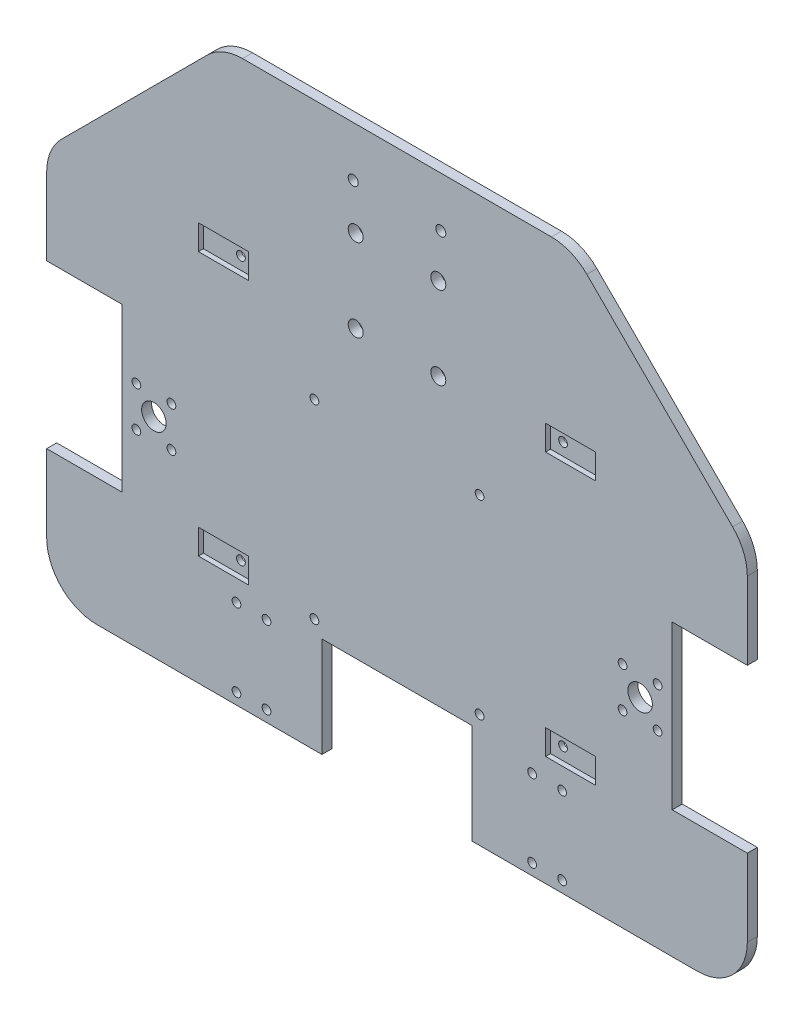
SolidWorks part; units mm, degrees
ref_plane "前视基准面" through (0, 0, 0) normal (0, 0, 1) x (1, 0, 0)
ref_plane "上视基准面" through (0, 0, 0) normal (0, 1, 0) x (1, 0, 0)
ref_plane "右视基准面" through (0, 0, 0) normal (1, 0, 0) x (0, 0, -1)
sketch "草图3" plane through (0, 0, 0) normal (0, 0, 1) x (1, 0, 0)
  line L1 (73.5057, 259.0895) -> (196.9372, 259.0895)
  line L2 (-4.7785, 180.8052) -> (-4.7785, 54.0895)
  line L3 (15.2215, 34.0895) -> (255.2215, 34.0895)
  line L4 (275.2215, 180.8052) -> (275.2215, 54.0895)
  line L6 (1.0793, 194.9474) -> (59.3636, 253.2316)
  line L9 (211.0793, 253.2316) -> (269.3636, 194.9474)
  arc A0 (73.5057, 259.0895) -> (59.3636, 253.2316) centre (73.5057, 239.0895) ccw
  arc A1 (211.0793, 253.2316) -> (196.9372, 259.0895) centre (196.9372, 239.0895) ccw
  arc A2 (1.0793, 194.9474) -> (-4.7785, 180.8052) centre (15.2215, 180.8052) ccw
  arc A3 (-4.7785, 54.0895) -> (15.2215, 34.0895) centre (15.2215, 54.0895) ccw
  arc A4 (255.2215, 34.0895) -> (275.2215, 54.0895) centre (255.2215, 54.0895) ccw
  arc A5 (275.2215, 180.8052) -> (269.3636, 194.9474) centre (255.2215, 180.8052) ccw
  dimension "D1" = 20
  dimension "D2" = 20
  dimension "D3" = 20
extrude "凸台-拉伸1" add sketch "草图3" along normal blind 4
sketch "电池槽" plane through (0, 0, 0) normal (0, 0, 1) x (1, 0, 0)
  line L0 (135.2215, 259.0895) -> (135.2215, 34.0895) construction
  line L6 (59.3636, 253.2316) -> (1.0793, 194.9474)
  line L7 (-4.7785, 180.8052) -> (-4.7785, 54.0895)
  line L8 (15.2215, 34.0895) -> (255.2215, 34.0895)
  line L9 (275.2215, 54.0895) -> (275.2215, 180.8052)
  line L10 (269.3636, 194.9474) -> (211.0793, 253.2316)
  line L11 (196.9372, 259.0895) -> (73.5057, 259.0895)
  line L12 (59.3636, 253.2316) -> (1.0793, 194.9474)
  line L13 (-4.7785, 180.8052) -> (-4.7785, 54.0895)
  line L14 (15.2215, 34.0895) -> (255.2215, 34.0895)
  line L15 (275.2215, 54.0895) -> (275.2215, 180.8052)
  line L16 (269.3636, 194.9474) -> (211.0793, 253.2316)
  line L17 (196.9372, 259.0895) -> (73.5057, 259.0895)
  line L21 (-4.7785, 117.4474) -> (275.2215, 117.4474) construction
  line L22 (95.2215, 162.4474) -> (175.2215, 162.4474)
  line L24 (105.2215, 152.4474) -> (165.2215, 152.4474)
  line L25 (105.2215, 152.4474) -> (105.2215, 82.4474)
  line L26 (105.2215, 82.4474) -> (165.2215, 82.4474)
  line L27 (165.2215, 152.4474) -> (165.2215, 82.4474)
  line L28 (105.2215, 152.4474) -> (165.2215, 82.4474) construction
  line L29 (105.2215, 82.4474) -> (165.2215, 152.4474) construction
  line L30 (175.2215, 162.4474) -> (175.2215, 72.4474)
  line L31 (95.2215, 72.4474) -> (175.2215, 72.4474)
  line L32 (95.2215, 162.4474) -> (95.2215, 72.4474)
  line L33 (95.2215, 162.4474) -> (105.2215, 152.4474) construction
  line L34 (105.2215, 82.4474) -> (95.2215, 72.4474) construction
  line L35 (165.2215, 82.4474) -> (175.2215, 72.4474) construction
  line L36 (165.2215, 152.4474) -> (175.2215, 162.4474) construction
  line L37 (97.2215, 160.4474) -> (173.2215, 160.4474)
  line L38 (173.2215, 160.4474) -> (173.2215, 74.4474)
  line L39 (97.2215, 74.4474) -> (173.2215, 74.4474)
  line L40 (97.2215, 160.4474) -> (97.2215, 74.4474)
  arc A6 (73.5057, 259.0895) -> (59.3636, 253.2316) centre (73.5057, 239.0895) ccw
  arc A7 (1.0793, 194.9474) -> (-4.7785, 180.8052) centre (15.2215, 180.8052) ccw
  arc A8 (-4.7785, 54.0895) -> (15.2215, 34.0895) centre (15.2215, 54.0895) ccw
  arc A9 (255.2215, 34.0895) -> (275.2215, 54.0895) centre (255.2215, 54.0895) ccw
  arc A10 (275.2215, 180.8052) -> (269.3636, 194.9474) centre (255.2215, 180.8052) ccw
  arc A11 (211.0793, 253.2316) -> (196.9372, 259.0895) centre (196.9372, 239.0895) ccw
  arc A12 (73.5057, 259.0895) -> (59.3636, 253.2316) centre (73.5057, 239.0895) ccw
  arc A13 (1.0793, 194.9474) -> (-4.7785, 180.8052) centre (15.2215, 180.8052) ccw
  arc A14 (-4.7785, 54.0895) -> (15.2215, 34.0895) centre (15.2215, 54.0895) ccw
  arc A15 (255.2215, 34.0895) -> (275.2215, 54.0895) centre (255.2215, 54.0895) ccw
  arc A16 (275.2215, 180.8052) -> (269.3636, 194.9474) centre (255.2215, 180.8052) ccw
  arc A17 (211.0793, 253.2316) -> (196.9372, 259.0895) centre (196.9372, 239.0895) ccw
  circle A20 centre (168.2215, 155.4474) radius 1.75
  circle A21 centre (168.2215, 79.4474) radius 1.75
  circle A22 centre (102.2215, 79.4474) radius 1.75
  circle A23 centre (102.2215, 155.4474) radius 1.75
  point P18 (135.2215, 117.4474)
  dimension "D3" = 8
  dimension "D2" = 10
  dimension "D1" = 0
sketch "轮槽" plane through (0, 0, 4) normal (0, 0, 1) x (1, 0, 0)
  line L4 (245.2215, 84.9474) -> (275.2215, 84.9474)
  line L5 (-4.7785, 149.9474) -> (7.2215, 149.9474)
  line L6 (59.3636, 253.2316) -> (1.0793, 194.9474)
  line L7 (-4.7785, 180.8052) -> (-4.7785, 54.0895)
  line L8 (15.2215, 34.0895) -> (255.2215, 34.0895)
  line L9 (275.2215, 54.0895) -> (275.2215, 180.8052)
  line L10 (269.3636, 194.9474) -> (211.0793, 253.2316)
  line L11 (196.9372, 259.0895) -> (73.5057, 259.0895)
  line L12 (59.3636, 253.2316) -> (1.0793, 194.9474)
  line L13 (-4.7785, 180.8052) -> (-4.7785, 54.0895)
  line L14 (15.2215, 34.0895) -> (255.2215, 34.0895)
  line L15 (275.2215, 54.0895) -> (275.2215, 180.8052)
  line L16 (269.3636, 194.9474) -> (211.0793, 253.2316)
  line L17 (196.9372, 259.0895) -> (73.5057, 259.0895)
  line L18 (7.2215, 149.9474) -> (25.2215, 149.9474)
  line L19 (25.2215, 149.9474) -> (25.2215, 84.9474)
  line L20 (25.2215, 84.9474) -> (-4.7785, 84.9474)
  line L21 (245.2215, 149.9474) -> (245.2215, 84.9474)
  line L22 (275.2215, 149.9474) -> (263.2215, 149.9474)
  line L23 (263.2215, 149.9474) -> (245.2215, 149.9474)
  arc A6 (73.5057, 259.0895) -> (59.3636, 253.2316) centre (73.5057, 239.0895) ccw
  arc A7 (1.0793, 194.9474) -> (-4.7785, 180.8052) centre (15.2215, 180.8052) ccw
  arc A8 (-4.7785, 54.0895) -> (15.2215, 34.0895) centre (15.2215, 54.0895) ccw
  arc A9 (255.2215, 34.0895) -> (275.2215, 54.0895) centre (255.2215, 54.0895) ccw
  arc A10 (275.2215, 180.8052) -> (269.3636, 194.9474) centre (255.2215, 180.8052) ccw
  arc A11 (211.0793, 253.2316) -> (196.9372, 259.0895) centre (196.9372, 239.0895) ccw
  arc A12 (73.5057, 259.0895) -> (59.3636, 253.2316) centre (73.5057, 239.0895) ccw
  arc A13 (1.0793, 194.9474) -> (-4.7785, 180.8052) centre (15.2215, 180.8052) ccw
  arc A14 (-4.7785, 54.0895) -> (15.2215, 34.0895) centre (15.2215, 54.0895) ccw
  arc A15 (255.2215, 34.0895) -> (275.2215, 54.0895) centre (255.2215, 54.0895) ccw
  arc A16 (275.2215, 180.8052) -> (269.3636, 194.9474) centre (255.2215, 180.8052) ccw
  arc A17 (211.0793, 253.2316) -> (196.9372, 259.0895) centre (196.9372, 239.0895) ccw
  line M18 (-4.7785, 180.8052) -> (-4.7785, 54.0895)
  line M22 (275.2215, 54.0895) -> (275.2215, 180.8052)
  dimension "D1" = 0
sketch "电机" plane through (0, 0, 0) normal (0, 0, 1) x (1, 0, 0)
  line L1 (31.0715, 125.4474) -> (45.0715, 125.4474) construction
  line L7 (25.2215, 130.6974) -> (53.2215, 130.6974) construction
  line L8 (245.2215, 122.9274) -> (237.0715, 122.9274) construction
  line L9 (45.0715, 125.4474) -> (31.0715, 125.4474) construction
  line L26 (53.2215, 130.6974) -> (53.2215, 104.1974) construction
  line L27 (25.2215, 117.4474) -> (33.3715, 117.4474) construction
  line L28 (217.2215, 122.9274) -> (225.3715, 122.9274) construction
  line L29 (225.3715, 122.9274) -> (225.3715, 130.9274) construction
  line L30 (25.2215, 111.9674) -> (25.2215, 104.1974) construction
  line L31 (239.3715, 130.9274) -> (225.3715, 130.9274) construction
  line L32 (232.3715, 130.9274) -> (232.3715, 114.9274) construction
  line L33 (237.0715, 122.9274) -> (225.3715, 122.9274) construction
  line L34 (225.3715, 114.9274) -> (239.3715, 114.9274) construction
  line L35 (135.2215, 259.0895) -> (135.2215, 34.0895) construction
  line L36 (196.9372, 259.0895) -> (73.5057, 259.0895) construction
  line L37 (15.2215, 34.0895) -> (255.2215, 34.0895) construction
  line L39 (45.0715, 117.4474) -> (45.0715, 125.4474) construction
  line L40 (45.0715, 109.4474) -> (31.0715, 109.4474) construction
  line L41 (38.0715, 125.4474) -> (38.0715, 109.4474) construction
  line L44 (25.2215, 111.9674) -> (25.2215, 130.6974) construction
  line L45 (53.2215, 104.1974) -> (25.2215, 104.1974) construction
  line L51 (53.2215, 117.4474) -> (45.0715, 117.4474) construction
  line L53 (245.2215, 117.4474) -> (245.2215, 109.6774) construction
  line L63 (237.0715, 117.4474) -> (225.3715, 117.4474) construction
  line L64 (245.2215, 111.9674) -> (245.2215, 130.6974) construction
  line L65 (217.2215, 130.6974) -> (217.2215, 104.1974)
  line L66 (245.2215, 104.1974) -> (245.2215, 130.6974)
  line L67 (217.2215, 117.4474) -> (225.3715, 117.4474) construction
  line L68 (217.2215, 104.1974) -> (245.2215, 104.1974) construction
  line L69 (245.2215, 111.9674) -> (245.2215, 130.6974) construction
  line L70 (232.3715, 125.4474) -> (232.3715, 109.4474) construction
  line L71 (225.3715, 109.4474) -> (239.3715, 109.4474) construction
  line L72 (225.3715, 117.4474) -> (225.3715, 125.4474) construction
  line L73 (245.2215, 111.9674) -> (245.2215, 104.1974) construction
  line L74 (245.2215, 130.6974) -> (217.2215, 130.6974)
  line L75 (217.2215, 104.1974) -> (245.2215, 104.1974)
  line L76 (245.2215, 117.4474) -> (237.0715, 117.4474) construction
  line L77 (217.2215, 130.6974) -> (217.2215, 104.1974) construction
  line L78 (225.3715, 125.4474) -> (239.3715, 125.4474) construction
  line L79 (245.2215, 130.6974) -> (217.2215, 130.6974) construction
  line L80 (239.3715, 125.4474) -> (225.3715, 125.4474) construction
  line L81 (25.2215, 111.9674) -> (25.2215, 130.6974) construction
  line L82 (33.3715, 117.4474) -> (45.0715, 117.4474) construction
  line L83 (25.2215, 117.4474) -> (25.2215, 109.6774) construction
  line L84 (45.0715, 114.9274) -> (31.0715, 114.9274) construction
  line L85 (33.3715, 122.9274) -> (45.0715, 122.9274) construction
  line L86 (38.0715, 130.9274) -> (38.0715, 114.9274) construction
  line L87 (31.0715, 130.9274) -> (45.0715, 130.9274) construction
  line L88 (45.0715, 122.9274) -> (45.0715, 130.9274) construction
  line L89 (53.2215, 122.9274) -> (45.0715, 122.9274) construction
  line L90 (25.2215, 122.9274) -> (33.3715, 122.9274) construction
  line L91 (53.2215, 104.1974) -> (25.2215, 104.1974)
  line L92 (25.2215, 130.6974) -> (53.2215, 130.6974)
  line L93 (25.2215, 104.1974) -> (25.2215, 130.6974)
  line L94 (53.2215, 130.6974) -> (53.2215, 104.1974)
  circle A27 centre (225.3715, 109.4474) radius 1.75
  circle A28 centre (239.3715, 125.4474) radius 1.75
  circle A29 centre (232.3715, 117.4474) radius 4.9
  circle A30 centre (225.3715, 125.4474) radius 1.75
  circle A31 centre (239.3715, 109.4474) radius 1.75
  circle A32 centre (31.0715, 109.4474) radius 1.75
  circle A33 centre (45.0715, 125.4474) radius 1.75
  circle A34 centre (38.0715, 117.4474) radius 4.9
  circle A35 centre (31.0715, 125.4474) radius 1.75
  circle A36 centre (45.0715, 109.4474) radius 1.75
sketch "L298N" plane through (0, 0, 0) normal (0, 0, 1) x (1, 0, 0)
  line L4 (113.7215, 226.2684) -> (156.7215, 226.2684)
  line L5 (113.7215, 226.2684) -> (113.7215, 183.2684)
  line L6 (113.7215, 183.2684) -> (156.7215, 183.2684)
  line L7 (156.7215, 226.2684) -> (156.7215, 183.2684)
  line L8 (113.7215, 226.2684) -> (156.7215, 183.2684) construction
  line L9 (113.7215, 183.2684) -> (156.7215, 226.2684) construction
  circle A0 centre (118.7215, 188.2684) radius 3
  circle A2 centre (118.7215, 221.2684) radius 3
  circle A3 centre (151.7215, 221.2684) radius 3
  circle A4 centre (151.7215, 188.2684) radius 3
  point P6 (135.2215, 204.7684)
  point P28 (135.2215, 204.7684)
  dimension "D1" = 4
extrude "切除-拉伸5" cut sketch "L298N" along normal blind 10 contours A0 | A2 | A4 | A3
extrude "切除-拉伸7" cut sketch "电池槽" along normal blind 10 contours A22 | A23 | A20 | A21
extrude "切除-拉伸8" cut sketch "轮槽" against normal blind 10 contours L20 L19 L18 L5 M18 | L22 L23 L21 L4 M22 region at (260.2215, 117.4474, 4) region at (10.2215, 117.4474, 4)
sketch "万向轮" plane through (0, 0, 0) normal (0, 0, 1) x (1, 0, 0)
  line L0 (135.2215, 259.0895) -> (135.2215, 219.0895) construction
  line L1 (196.9372, 259.0895) -> (73.5057, 259.0895) construction
  line L2 (158.7215, 239.0895) -> (111.7215, 239.0895) construction
  line L3 (152.7215, 239.0895) -> (117.7215, 239.0895)
  line L4 (111.7215, 239.0895) -> (125.647, 250.6363)
  line L5 (158.7215, 239.0895) -> (144.796, 250.6363)
  line L6 (158.7215, 239.0895) -> (144.796, 227.5426)
  line L7 (111.7215, 239.0895) -> (125.647, 227.5426)
  circle A0 centre (117.7215, 239.0895) radius 2
  circle A1 centre (152.7215, 239.0895) radius 2
  circle A2 centre (135.2215, 239.0895) radius 13.5
  circle A3 centre (135.2215, 239.0895) radius 15
  point P7 (135.2215, 239.0895)
  point P10 (135.2215, 239.0895)
extrude "切除-拉伸10" cut sketch "万向轮" along normal blind 10 contours A0 | A1 region at (152.7215, 241.0329, 0) region at (115.778, 239.0895, 0)
extrude "切除-拉伸3" cut sketch "电机" along normal blind 10 contours A32 | A33 | A34 | A35 | A36 | A30 | A28 | A31 | A27 | A29
ref_plane "基准面1" through (0, 0, 4) normal (0, 0, 1) x (1, 0, 0)
sketch "草图11" plane through (0, 0, 4) normal (0, 0, 1) x (1, 0, 0)
  line L0 (-3.2561, 188.4589) -> (273.6991, 188.4589) construction
  line L1 (65.8521, 132.7742) -> (204.5909, 132.7742) construction
  line L2 (15.2215, 34.0895) -> (255.2215, 34.0895) construction
  line L3 (204.5909, 257.5671) -> (204.5909, 34.0895) construction
  line L4 (-4.7785, 54.0895) -> (275.2215, 54.0895) construction
  line L6 (55.8521, 193.4589) -> (75.8521, 193.4589)
  line L7 (55.8521, 193.4589) -> (55.8521, 183.4589)
  line L8 (55.8521, 183.4589) -> (75.8521, 183.4589)
  line L9 (75.8521, 193.4589) -> (75.8521, 183.4589)
  line L10 (55.8521, 193.4589) -> (75.8521, 183.4589) construction
  line L11 (55.8521, 183.4589) -> (75.8521, 193.4589) construction
  line L14 (55.8521, 88.0895) -> (75.8521, 78.0895) construction
  line L15 (55.8521, 78.0895) -> (75.8521, 88.0895) construction
  line L16 (75.8521, 78.0895) -> (75.8521, 88.0895)
  line L17 (55.8521, 88.0895) -> (75.8521, 88.0895)
  line L18 (55.8521, 78.0895) -> (55.8521, 88.0895)
  line L19 (55.8521, 78.0895) -> (75.8521, 78.0895)
  line L20 (214.5909, 78.0895) -> (194.5909, 88.0895) construction
  line L21 (214.5909, 88.0895) -> (194.5909, 78.0895) construction
  line L22 (214.5909, 183.4589) -> (194.5909, 193.4589) construction
  line L23 (214.5909, 193.4589) -> (194.5909, 183.4589) construction
  line L24 (214.5909, 78.0895) -> (194.5909, 78.0895)
  line L25 (214.5909, 78.0895) -> (214.5909, 88.0895)
  line L26 (214.5909, 88.0895) -> (194.5909, 88.0895)
  line L27 (194.5909, 78.0895) -> (194.5909, 88.0895)
  line L28 (194.5909, 193.4589) -> (194.5909, 183.4589)
  line L29 (214.5909, 183.4589) -> (194.5909, 183.4589)
  line L30 (214.5909, 193.4589) -> (214.5909, 183.4589)
  line L31 (214.5909, 193.4589) -> (194.5909, 193.4589)
  arc A0 (1.0793, 194.9474) -> (-4.7785, 180.8052) centre (15.2215, 180.8052) ccw construction
  arc A1 (275.2215, 180.8052) -> (269.3636, 194.9474) centre (255.2215, 180.8052) ccw construction
  circle A2 centre (70.8521, 83.0895) radius 1.75
  arc A3 (211.0793, 253.2316) -> (196.9372, 259.0895) centre (196.9372, 239.0895) ccw construction
  arc A4 (-4.7785, 54.0895) -> (15.2215, 34.0895) centre (15.2215, 54.0895) ccw construction
  circle A9 centre (70.8521, 188.4589) radius 1.75
  circle A10 centre (199.5909, 83.0895) radius 1.75
  circle A11 centre (199.5909, 188.4589) radius 1.75
  point P26 (0, 0)
extrude "切除-拉伸11" cut sketch "草图11" against normal blind 2 contours L9 L6 L7 L8 A9 | L18 L19 L16 L17 A2 | L31 L28 L29 L30 | L26 L27 L24 L25 region at (65.5994, 188.4589, 4) region at (65.5994, 83.0895, 4)
ref_plane "基准面2" through (0, 0, 4) normal (0, 0, 1) x (1, 0, 0)
sketch "草图12" plane through (0, 0, 4) normal (0, 0, 1) x (1, 0, 0)
  line L0 (105.2215, 34.0895) -> (165.2215, 34.0895)
  line L1 (165.2215, -5.9105) -> (105.2215, -5.9105)
  line L2 (165.2215, -5.9105) -> (165.2215, 74.0895)
  line L3 (165.2215, 74.0895) -> (105.2215, 74.0895)
  line L4 (105.2215, -5.9105) -> (105.2215, 74.0895)
  line L5 (165.2215, -5.9105) -> (105.2215, 74.0895) construction
  line L6 (165.2215, 74.0895) -> (105.2215, -5.9105) construction
  point P0 (135.2215, 34.0895)
extrude "切除-拉伸12" cut sketch "草图12" against normal blind 10 contours L4 L0 L2 L3 region at (135.2215, 54.0895, 4)
extrude "切除-拉伸13" cut sketch "草图11<3>" against normal blind 10 contours A9 | A11 | A10 | A2 region at (70.8521, 83.0895, 4) region at (70.8521, 188.4589, 4) region at (199.5909, 83.0895, 4) region at (199.5909, 188.4589, 4)
sketch "草图11<3>" plane through (0, 0, 4) normal (0, 0, 1) x (1, 0, 0) same geometry as "草图11"
sketch "草图13" plane through (0, 0, 4) normal (0, 0, 1) x (1, 0, 0)
  line L0 (105.2215, 34.0895) -> (93.5715, 34.0895) construction
  line L1 (105.2215, 34.0895) -> (105.2215, 74.0895) construction
  line L2 (15.2215, 34.0895) -> (255.2215, 34.0895) construction
  line L3 (93.5715, 34.0895) -> (84.7215, 34.0895) construction
  line L4 (84.7215, 34.0895) -> (81.4215, 34.0895) construction
  line L5 (81.4215, 34.0895) -> (72.7215, 34.0895) construction
  line L6 (72.7215, 34.0895) -> (69.4215, 34.0895) construction
  line L7 (105.2215, 34.0895) -> (105.2215, 74.0895) construction
  line L9 (105.2215, 38.5895) -> (58.9496, 38.5895) construction
  line L10 (105.2215, 74.0895) -> (83.0715, 74.0895) construction
  line L11 (83.0715, 74.0895) -> (71.0715, 74.0895) construction
  line L12 (105.2215, 54.0895) -> (57.599, 54.0895) construction
  line L13 (165.2215, 54.0895) -> (224.665, 54.0895) construction
  line L14 (165.2215, 34.0895) -> (165.2215, 74.0895) construction
  line L16 (189.2215, 69.5895) -> (201.2215, 69.5895) construction
  line L17 (165.2215, 74.0895) -> (165.2215, 69.5895) construction
  line L18 (165.2215, 69.5895) -> (201.2215, 69.5895) construction
  circle A0 centre (83.0715, 38.5895) radius 1.75
  circle A1 centre (71.0715, 38.5895) radius 1.75
  circle A2 centre (71.0715, 69.5895) radius 1.75
  circle A3 centre (83.0715, 69.5895) radius 1.75
  circle A4 centre (189.2215, 69.5895) radius 1.75
  circle A5 centre (201.2215, 69.5895) radius 1.75
  circle A6 centre (201.2215, 38.5895) radius 1.75
  circle A7 centre (189.2215, 38.5895) radius 1.75
extrude "切除-拉伸14" cut sketch "草图13" against normal through all
